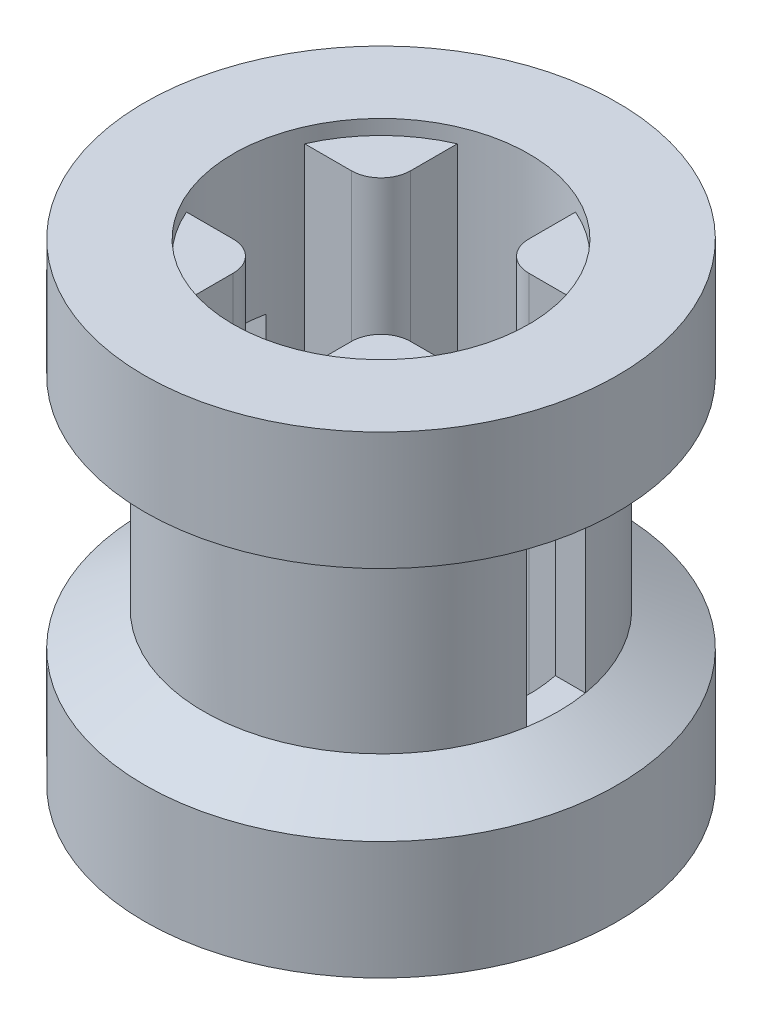
SolidWorks part; units mm, degrees
ref_plane "Front Plane" through (0, 0, 0) normal (0, 0, 1) x (1, 0, 0)
ref_plane "Top Plane" through (0, 0, 0) normal (0, 1, 0) x (1, 0, 0)
ref_plane "Right Plane" through (0, 0, 0) normal (1, 0, 0) x (0, 0, -1)
sketch "Sketch1" plane through (0, 0, 0) normal (0, 1, 0) x (1, 0, 0)
  circle A0 centre (0, 0) radius 3
  circle A1 centre (0, 0) radius 2.5
  dimension "D1" = 6
  dimension "D2" = 5
extrude "Boss-Extrude1" add sketch "Sketch1" along normal blind 8
sketch "Sketch3" plane through (0, 0, 0) normal (0, 1, 0) x (1, 0, 0)
  line L0 (1, 2.2913) -> (1, 1.5)
  line L1 (2.2913, 1) -> (1.5, 1)
  line L2 (1, -2.2913) -> (1, -1.5)
  line L3 (2.2913, -1) -> (1.5, -1)
  line L4 (-2.2913, -1) -> (-1.5, -1)
  line L5 (-1, -2.2913) -> (-1, -1.5)
  line L6 (-1, 2.2913) -> (-1, 1.5)
  line L7 (-2.2913, 1) -> (-1.5, 1)
  circle A0 centre (0, 0) radius 2.5 construction
  arc A1 (1, 1.5) -> (1.5, 1) centre (1.5, 1.5) ccw
  arc A2 (1, 2.2913) -> (2.2913, 1) centre (0, 0) cw
  arc A3 (2.2913, -1) -> (1, -2.2913) centre (0, 0) cw
  arc A4 (1.5, -1) -> (1, -1.5) centre (1.5, -1.5) ccw
  arc A5 (-1, -2.2913) -> (-2.2913, -1) centre (0, 0) cw
  arc A6 (-1, -1.5) -> (-1.5, -1) centre (-1.5, -1.5) ccw
  arc A7 (-2.2913, 1) -> (-1, 2.2913) centre (0, 0) cw
  arc A8 (-1.5, 1) -> (-1, 1.5) centre (-1.5, 1.5) ccw
  point P8 (1, 1.8956)
  point P28 (0, 0)
  dimension "D1" = 0.5
  dimension "D4" = 2.5
  dimension "D2" = 1
  dimension "D3" = 1
  dimension "D5" = 4
extrude "Boss-Extrude2" add sketch "Sketch3" along normal blind 7.5 from offset 0.25
sketch "Sketch4" plane through (0, 0, 0) normal (0, 1, 0) x (1, 0, 0)
  circle A0 centre (0, 0) radius 4
  circle A1 centre (0, 0) radius 3
  dimension "D1" = 8
  dimension "D2" = 6
extrude "Boss-Extrude3" add sketch "Sketch4" along normal blind 2
extrude "Boss-Extrude4" add sketch "Sketch4<2>" against normal blind 2 from offset 8
sketch "Sketch4<2>" plane through (0, 0, 0) normal (0, 1, 0) x (1, 0, 0) same geometry as "Sketch4"
sketch "Sketch5" plane through (0, 0, 0) normal (1, 0, 0) x (0, 0, -1)
  line L0 (3, 2.5774) -> (4, 2)
  line L1 (3, 2) -> (3, 6) construction
  line L2 (3, 2.5774) -> (3, 2)
  line L3 (3, 2) -> (4, 2)
  line L4 (0, -0.5127) -> (0, 1.6921) construction
  line L5 (3, 6) -> (4, 6)
  line L6 (4, 6) -> (3, 5.4226)
  line L7 (3, 5.4226) -> (3, 6)
  line L8 (-3, 6) -> (3, 6) construction
  dimension "D1" = 30
  dimension "D2" = 30
revolve "Revolve1" add sketch "Sketch5" angle 360 about L4
sketch "Sketch6" plane through (0, 0, 0) normal (1, 0, 0) x (0, 0, -1)
  line L0 (-0.5, 2.5774) -> (-0.5, 5.4226)
  line L1 (3, 2.5774) -> (-3, 2.5774) construction
  line L2 (3, 5.4226) -> (-3, 5.4226) construction
  line L3 (-0.5, 5.4226) -> (0.5, 5.4226)
  line L4 (0.5, 5.4226) -> (0.5, 2.5774)
  line L5 (0.5, 2.5774) -> (-0.5, 2.5774)
  line L6 (0, 0) -> (0, 8) construction
  line L7 (-4, 0) -> (4, 0) construction
  line L8 (2.5, 8) -> (-2.5, 8) construction
  dimension "D1" = 1
extrude "Cut-Extrude1" cut sketch "Sketch6" against normal blind 10 and the other way blind 10
